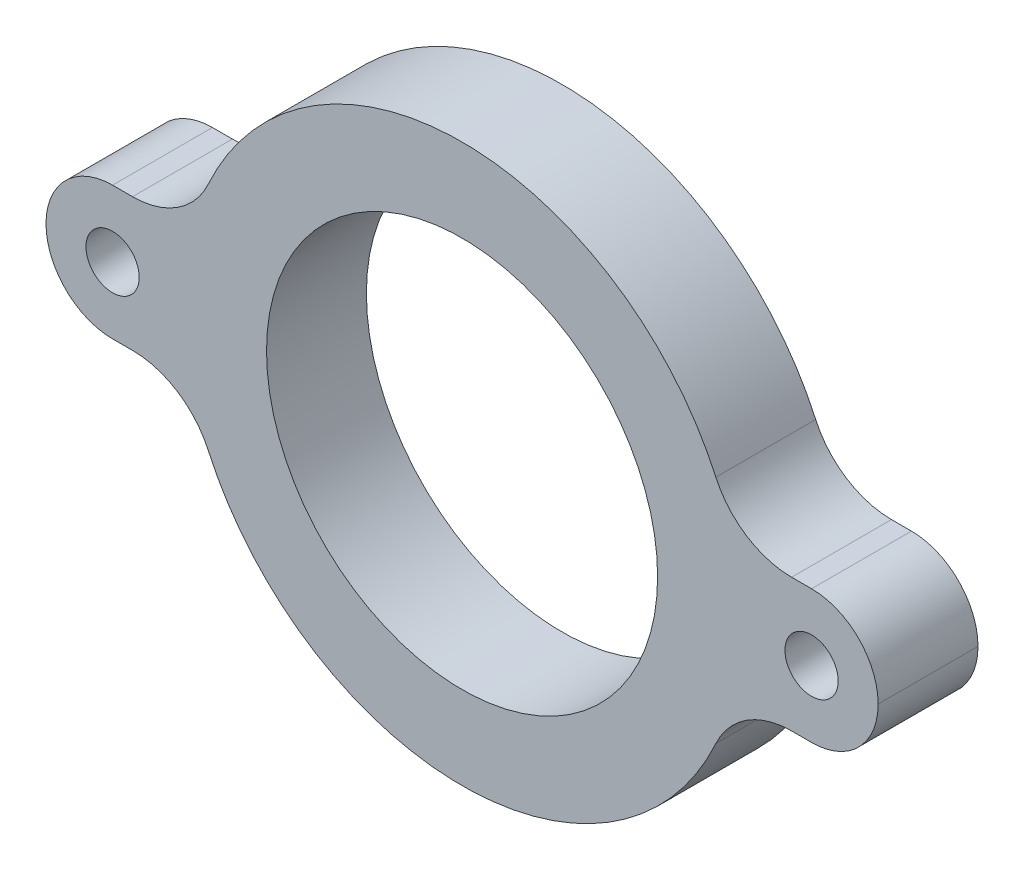
SolidWorks part; units mm, degrees
material "MDF"
ref_plane "Plano frontal" through (0, 0, 0) normal (0, 0, 1) x (1, 0, 0)
ref_plane "Plano superior" through (0, 0, 0) normal (0, 1, 0) x (1, 0, 0)
ref_plane "Plano direito" through (0, 0, 0) normal (1, 0, 0) x (0, 0, -1)
sketch "Esboço1" plane through (0, 0, 0) normal (0, 0, 1) x (1, 0, 0)
  line L0 (-19.5214, 0) -> (-12, 0) construction
  line L1 (-21, 0) -> (21, 0) construction
  line L2 (-25, 4) -> (-16.2654, 4)
  line L3 (0, 0) -> (0, 11.75) construction
  line L4 (25, 4) -> (16.2654, 4)
  line L5 (25, -4) -> (16.2654, -4)
  line L6 (-25, -4) -> (-16.2654, -4)
  line L7 (-25, -4) -> (-25, 4)
  line L8 (25, 4) -> (25, -4)
  circle A0 centre (0, 0) radius 11.75
  circle A1 centre (0, 0) radius 12 construction
  circle A3 centre (-21, 0) radius 1.6
  circle A4 centre (21, 0) radius 1.6
  arc A5 (-16.2654, 4) -> (16.2654, 4) centre (0, 0) cw
  arc A6 (-16.2654, -4) -> (16.2654, -4) centre (0, 0) ccw
  circle A7 centre (-13.5, 0) radius 3 construction
  point P5 (-12, 0)
  point P6 (-19.5214, 0)
  point P18 (0, 16.75)
  point P22 (0, 12)
  point P23 (0, 11.75)
  dimension "D1" = 23.5
  dimension "D2" = 24
  dimension "D3" = 3.2
  dimension "D7" = 5
  dimension "D4" = 6
  dimension "D8" = 27
  dimension "D5" = 4
  dimension "D6" = 4
  dimension "D9" = 7.5
extrude "Ressalto-extrusão1" add sketch "Esboço1" along normal blind 6
fillet "Filete2" radius 5 4 edges at (16.2654, 4, 3) (16.2654, -4, 3) (-16.2654, -4, 3) (-16.2654, 4, 3)
fillet "Filete3" radius 4 4 edges at (25, -4, 3) (25, 4, 3) (-25, -4, 3) (-25, 4, 3)
